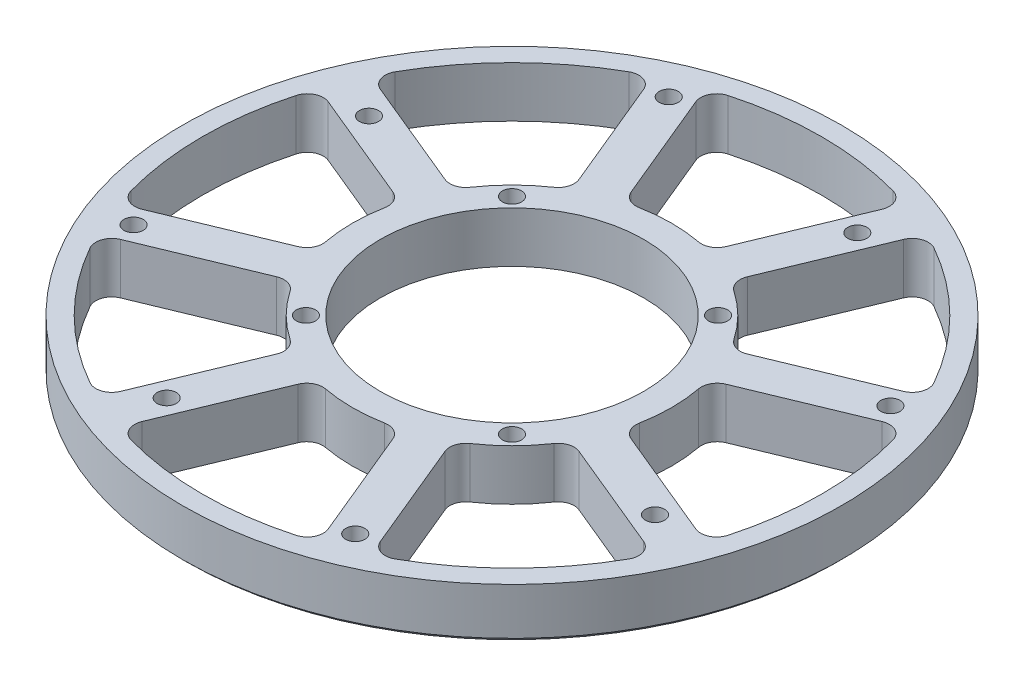
SolidWorks part; units mm, degrees
material "6061-T6 (SS)"
ref_plane "Front Plane" through (0, 0, 0) normal (0, 0, 1) x (1, 0, 0)
ref_plane "Top Plane" through (0, 0, 0) normal (0, 1, 0) x (1, 0, 0)
ref_plane "Right Plane" through (0, 0, 0) normal (1, 0, 0) x (0, 0, -1)
sketch "Sketch2" plane through (0, 0, 0) normal (1, 0, 0) x (0, 0, -1)
  line L0 (0, 0) -> (-82.55, 0)
  line L1 (-82.55, 0) -> (-82.55, 12.7)
  line L2 (-82.55, 12.7) -> (0, 12.7)
  line L5 (0, 12.7) -> (0, 0)
  dimension "D1" = 82.55
  dimension "D2" = 12.7
ref_axis "Axis1" through (0, -0.635, 0) along (0, 1, 0)
revolve "Revolve1" add sketch "Sketch2" angle 360 about axis through (0, -0.635, 0) along (0, 1, 0)
hole_wizard "#12 (0.189) Diameter Hole1" positions "Sketch6" profile "Sketch7" hole size "#12" standard "ANSI Inch" end condition through all
sketch "Sketch6" plane through (0, 12.7, 0) normal (0, 1, 0) x (1, 0, 0)
  line L0 (0, 0) -> (-53.438, 129.0108) construction
  line L2 (0, 0) -> (0, 109.0908) construction
  line L3 (0, 0) -> (-76.2663, 31.5905) construction
  line L4 (0, 0) -> (-68.4315, 68.4315) construction
  circle A0 centre (0, 0) radius 82.55 construction
  point P0 (-27.7637, 67.0275)
  point P18 (-61.1608, 25.3336)
  point P27 (-25.8094, 25.8094)
  dimension "D1" = 22.5
  dimension "D2" = 72.55
  dimension "D3" = 45
  dimension "D4" = 66.2
  dimension "D6" = 22.5
  dimension "D5" = 36.5
sketch "Sketch7" plane through (-27.7637, 12.7, -67.0275) normal (1, 0, 0) x (0, 0, 1)
  line L0 (0, 0) -> (0, 12.7)
  line L1 (0, 12.7) -> (2.4003, 12.7)
  line L2 (2.4003, 12.7) -> (2.4003, 0)
  line L5 (2.4003, 0) -> (0, 0)
  line L11 (0, -6.35) -> (0, 107.95) construction
  dimension "Thru Hole Dia." = 4.8006
  dimension "Thru Hole Depth" = 12.7
pattern_circular "CirPattern3" count 4 over 360 about axis through (0, -0.635, 0) along (0, 1, 0) of "#12 (0.189) Diameter Hole1"
sketch "Sketch8" plane through (0, 12.7, 0) normal (0, 1, 0) x (1, 0, 0)
  line L4 (0, 0) -> (0, 93.9995) construction
  line L5 (0, 0) -> (113.8372, 0) construction
  line L6 (-10.5679, 38.5787) -> (-24.996, 73.4112)
  line L7 (10.5679, 38.5787) -> (24.996, 73.4112)
  line L8 (0, 0) -> (-27.7637, 67.0275) construction
  arc A0 (-10.5679, 38.5787) -> (10.5679, 38.5787) centre (0, 0) cw
  arc A1 (-24.996, 73.4112) -> (24.996, 73.4112) centre (0, 0) cw
  circle A2 centre (0, 0) radius 82.55 construction
  dimension "D1" = 40
  dimension "D2" = 5
  dimension "D3" = 5
extrude "Cut-Extrude1" cut sketch "Sketch8" against normal through all
fillet "Fillet1" radius 4 4 edges at (10.5679, 6.35, -38.5787) (24.996, 6.35, -73.4112) (-10.5679, 6.35, -38.5787) (-24.996, 6.35, -73.4112)
pattern_circular "CirPattern4" count 8 over 360 about axis through (0, -0.635, 0) along (0, 1, 0) of "Cut-Extrude1", "Fillet1"
chamfer "Chamfer2" distance 1 angle 45 1 edges at (0, 0, -82.55)
sketch "Sketch9" plane through (0, 12.7, 0) normal (0, 1, 0) x (1, 0, 0)
  circle A0 centre (0, 0) radius 33
  dimension "D1" = 66
extrude "Cut-Extrude2" cut sketch "Sketch9" against normal through all
equation "\"TubeDiameter\" = 6.500in"
equation "\"D1@Sketch2\"=\"TubeDiameter\"/2"
equation "\"D2@Sketch6\"=\"TubeDiameter\"/2-10mm"
